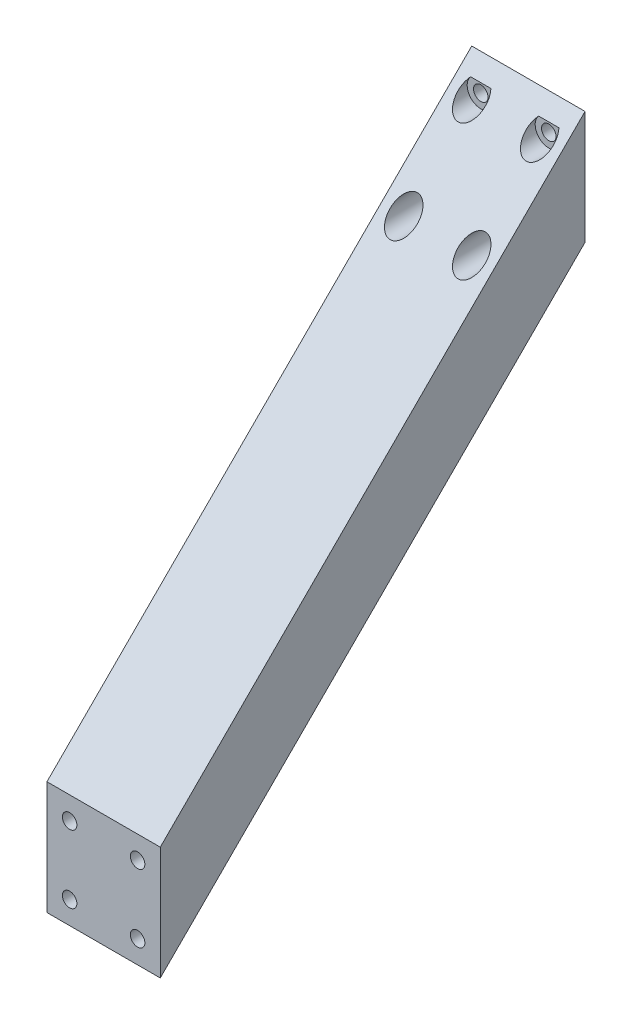
SolidWorks part; units mm, degrees
ref_plane "Front Plane" through (0, 0, 0) normal (0, 0, 1) x (1, 0, 0)
ref_plane "Top Plane" through (0, 0, 0) normal (0, 1, 0) x (1, 0, 0)
ref_plane "Right Plane" through (0, 0, 0) normal (1, 0, 0) x (0, 0, -1)
sketch "Sketch1" plane through (0, 0, 0) normal (1, 0, 0) x (0, 0, -1)
  line L0 (0, 40.3987) -> (0, -93.7099) construction
  line L1 (0, 0) -> (-93.7099, -93.7099)
  line L2 (0, -93.7099) -> (-93.7099, -93.7099) construction
  line L5 (0, 25) -> (0, 0)
  line L7 (-93.7099, -93.7099) -> (-93.7099, -68.7099)
  line L8 (-93.7099, -68.7099) -> (0, 25)
  dimension "D1" = 45
  dimension "D2" = 93.7099
  dimension "D3" = 93.7099
  dimension "D4" = 25
  dimension "D5" = 25
extrude "Boss-Extrude1" add sketch "Sketch1" along normal blind 25
sketch "Sketch3" plane through (0, 0, 0) normal (0, 0, -1) x (-1, 0, 0)
  line L2 (-20, 20) -> (-20, 5) construction
  line L3 (0, 0) -> (0, 25) construction
  line L4 (-25, 25) -> (0, 25) construction
  line L5 (-25, 0) -> (-25, 25) construction
  circle A0 centre (-20, 20) radius 1.6
  circle A1 centre (-20, 20) radius 3
  circle A2 centre (-20, 5) radius 3
  circle A3 centre (-20, 5) radius 1.6
  circle A4 centre (-5, 5) radius 3
  circle A5 centre (-5, 5) radius 1.6
  circle A6 centre (-5, 20) radius 3
  circle A7 centre (-5, 20) radius 1.6
  dimension "D1" = 6
  dimension "D2" = 3.2
  dimension "D3" = 5
  dimension "D4" = 5
  dimension "D7" = 15
  dimension "D8" = 5
  dimension "D5" = 2
  dimension "D6" = 2
extrude "Cut-Extrude7" cut sketch "Sketch3" against normal up to next from offset 3 offset against normal yes
extrude "Cut-Extrude8" cut sketch "Sketch3<3>" against normal up to next contours A7 | A0 | A5 | A3 region at (20, 20, 0) region at (20, 5, 0) region at (5, 5, 0) region at (5, 20, 0)
sketch "Sketch3<3>" plane through (0, 0, 0) normal (0, 0, -1) x (-1, 0, 0) same geometry as "Sketch3"
sketch "Sketch4" plane through (0, 0, 93.7099) normal (0, 0, 1) x (1, 0, 0)
  line L0 (5, -73.7099) -> (5, -33.9645) construction
  line L1 (25, -68.7099) -> (0, -68.7099) construction
  line L2 (0, -68.7099) -> (0, -93.7099) construction
  line L3 (5, -73.7099) -> (5, -88.7099) construction
  circle A0 centre (5, -73.7099) radius 1.6
  circle A1 centre (5, -73.7099) radius 3
  circle A8 centre (5, -88.7099) radius 1.6
  circle A9 centre (5, -88.7099) radius 3
  circle A10 centre (20, -88.7099) radius 1.6
  circle A11 centre (20, -88.7099) radius 3
  circle A12 centre (20, -73.7099) radius 1.6
  circle A13 centre (20, -73.7099) radius 3
  dimension "D1" = 6
  dimension "D2" = 3.2
  dimension "D3" = 5
  dimension "D4" = 5
  dimension "D7" = 15
  dimension "D5" = 2
  dimension "D6" = 2
extrude "Cut-Extrude9" cut sketch "Sketch4" against normal up to next from offset 3 offset against normal yes
extrude "Cut-Extrude10" cut sketch "Sketch4<2>" against normal up to next contours A0 | A12 | A10 | A8 region at (5, -73.7099, 93.7099) region at (5, -88.7099, 93.7099) region at (20, -88.7099, 93.7099) region at (20, -73.7099, 93.7099)
sketch "Sketch4<2>" plane through (0, 0, 93.7099) normal (0, 0, 1) x (1, 0, 0) same geometry as "Sketch4"
